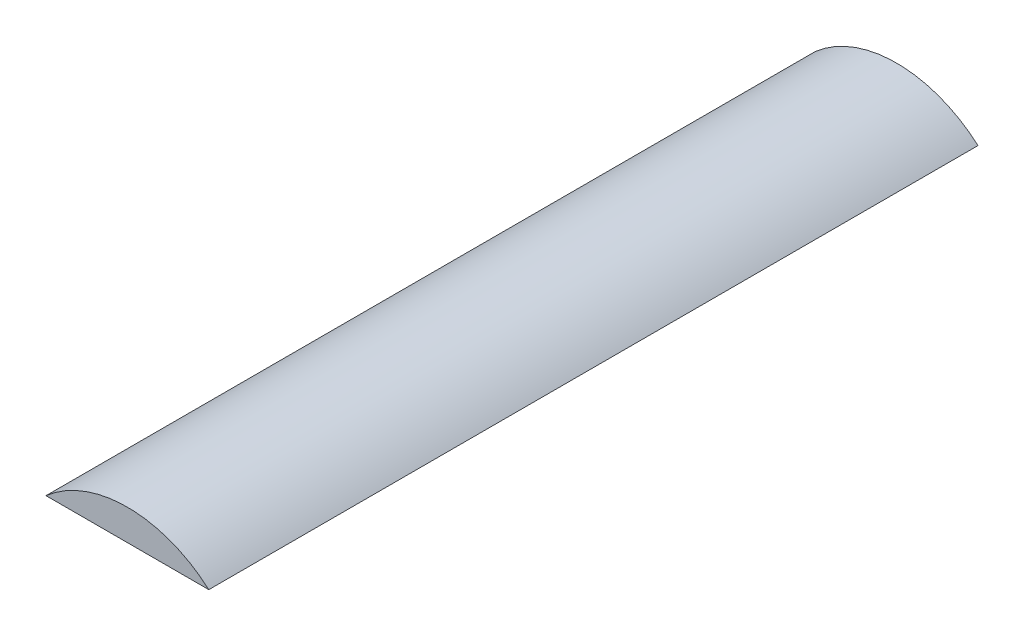
SolidWorks part; units mm, degrees
ref_plane "前视基准面" through (0, 0, 0) normal (0, 0, 1) x (1, 0, 0)
ref_plane "上视基准面" through (0, 0, 0) normal (0, 1, 0) x (1, 0, 0)
ref_plane "右视基准面" through (0, 0, 0) normal (1, 0, 0) x (0, 0, -1)
other "Configuration Table"
sketch "草图1" plane through (0, 0, 0) normal (0, 0, 1) x (1, 0, 0)
  line L1 (5, 5) -> (5, 1) construction
  line L2 (5, 1) -> (-5.583, 1)
  line L3 (5, 1) -> (15.583, 1)
  arc A0 (-5.583, 1) -> (15.583, 1) centre (5, -11) cw
  dimension "D1" = 16
  dimension "D2" = 4
extrude "凸台-拉伸1" add sketch "草图1" along normal blind 100
